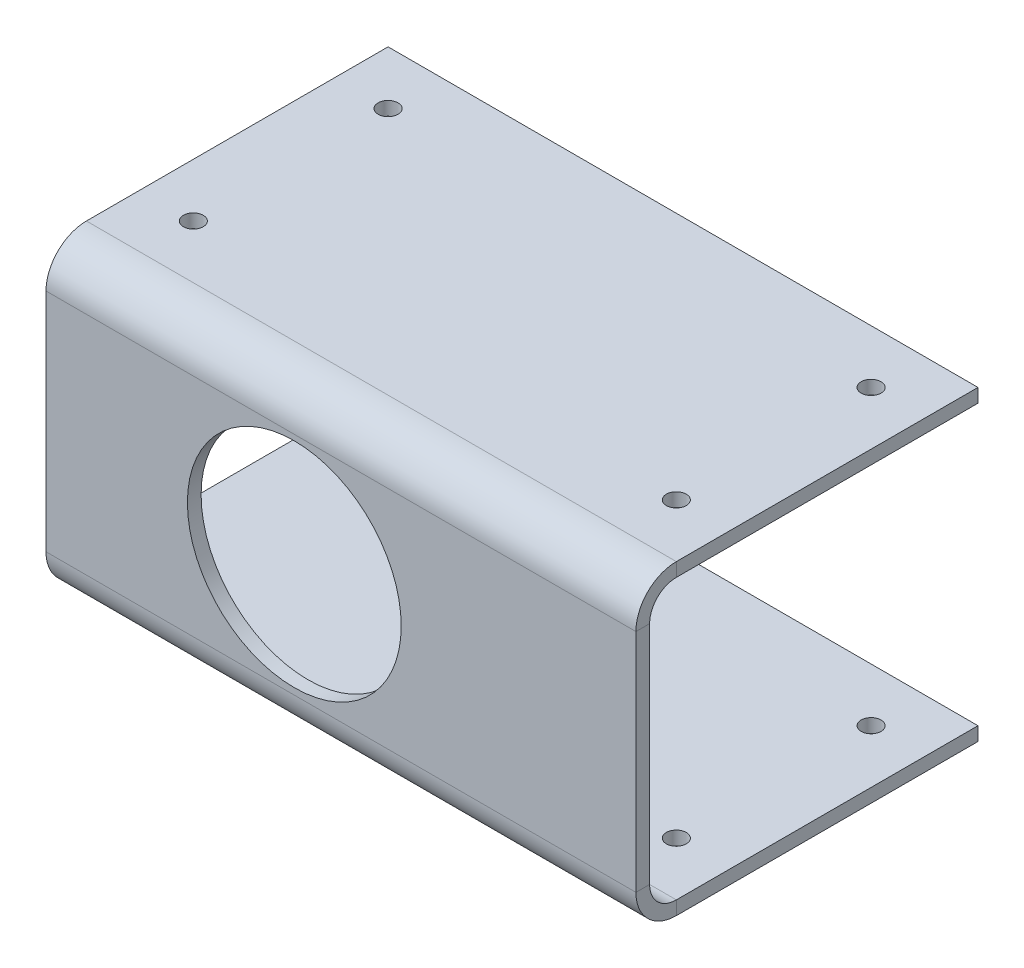
SolidWorks part; units mm, degrees
note: The reader was unsure of these and kept them because the rebuilt part matched: flange length of "Edge-Flange1".
material "6061-T6 (SS)"
ref_plane "Front Plane" through (0, 0, 0) normal (0, 0, 1) x (1, 0, 0)
ref_plane "Top Plane" through (0, 0, 0) normal (0, 1, 0) x (1, 0, 0)
ref_plane "Right Plane" through (0, 0, 0) normal (1, 0, 0) x (0, 0, -1)
sketch "Sketch1" plane through (0, 0, 0) normal (0, 0, 1) x (1, 0, 0)
  line L1 (-12.6221, 8.32) -> (16.07, 8.32)
  line L2 (-12.6221, 8.32) -> (-12.6221, -8.27)
  line L3 (-12.6221, -8.27) -> (16.07, -8.27)
  line L4 (-12.6221, -4.7) -> (-12.6221, 4.8) construction
  line L7 (16.07, -8.27) -> (22.42, -8.27)
  line L9 (16.07, 8.32) -> (22.42, 8.32)
  line L10 (22.42, -8.27) -> (22.42, 8.32)
  dimension "D1" = 6.35
base flange "Base-Flange1" sketch "Sketch1" thickness 0.8128 reverse thickness direction yes parameters "D1"=0.8128
edge flange "Edge-Flange1" sketch "Sketch10" flange profiles "Sketch10", "Sketch11" flange angle 90 flange length 20.32 flange position material outside bend radius 1.5875 thickness 0.8128 relief rectangular parameters "D6"=10, "D8"=1
sketch "Sketch10" plane through (0, -8.27, 0) normal (0, -1, 0) x (-1, 0, 0)
  line L0 (12.6221, 0) -> (-22.42, 0) construction
  line L1 (12.6221, 0) -> (-22.42, 0)
  line L2 (-22.42, 0) -> (-22.42, 19.5072)
  line L3 (-22.42, 19.5072) -> (12.6221, 19.5072)
  line L4 (12.6221, 19.5072) -> (12.6221, 0)
sketch "Sketch11" plane through (0, 8.32, 0) normal (0, 1, 0) x (1, 0, 0)
  line L0 (22.42, 0) -> (-12.6221, 0) construction
  line L1 (22.42, 0) -> (-12.6221, 0)
  line L2 (-12.6221, 0) -> (-12.6221, 19.5072)
  line L3 (-12.6221, 19.5072) -> (22.42, 19.5072)
  line L4 (22.42, 19.5072) -> (22.42, 0)
bend "EdgeBend1" bend radius 1.5875 bend angle 90 parameters "D5"=1
bend "EdgeBend2" bend radius 1.5875 bend angle 90 parameters "D5"=2
sketch "Sketch12" plane through (0, 0, 0.8128) normal (0, 0, 1) x (1, 0, 0)
  circle A0 centre (2.1279, 0.05) radius 6.35
  dimension "D1" = 12.7
extrude "Cut-Extrude1" cut sketch "Sketch12" against normal through all
hole_wizard "#56 (0.0465) Diameter Hole1" positions "Sketch14" profile "Sketch13" hole size "#56" standard "ANSI Inch" end condition through all
sketch "Sketch14" plane through (0, 9.1328, 0) normal (0, 1, 0) x (1, 0, 0)
  point P0 (19.245, 4.7625)
  point P3 (19.245, 16.3322)
  point P6 (-9.4471, 16.3322)
  point P9 (-9.4471, 4.7625)
sketch "Sketch13" plane through (19.245, 9.1328, -4.7625) normal (1, 0, 0) x (0, 0, 1)
  line L0 (0, 0) -> (0, 18.2156)
  line L1 (0, 18.2156) -> (0.5905, 18.2156)
  line L2 (0.5905, 18.2156) -> (0.5905, 0)
  line L5 (0.5905, 0) -> (0, 0)
  line L11 (0, -6.35) -> (0, 107.95) construction
  dimension "Thru Hole Dia." = 1.1811
  dimension "Thru Hole Depth" = 18.2156
sketch "Bend-Lines1" [suppressed] plane through (0, 0, 0) normal (0, 1, 0) x (1, 0, 0)
sketch "Bounding-Box1" [suppressed] plane through (0, 0, 0) normal (0, 1, 0) x (1, 0, 0)
sheet metal parameters "Sheet-Metal1" thickness 0.8128 parameters "D1"=0.8128
flat pattern "Flat-Pattern1" [suppressed]
sketch "Bend-Lines2" plane through (0, 0, 0) normal (0, 1, 0) x (1, 0, 0)
sketch3d "Bounding-Box2" [suppressed]
  line L0 (-15.97, -8.27, 0) -> (22.42, -8.27, 0) construction
  line L1 (-15.97, 8.32, 0) -> (22.42, 8.32, 0) construction
  line L2 (-15.97, -8.27, 0) -> (-15.97, 8.32, 0) construction
  line L3 (22.42, -8.27, 0) -> (22.42, 8.32, 0) construction
sheet metal parameters "Sheet-Metal2" thickness 0.8128 parameters "D1"=0.8128
flat pattern "Flat-Pattern1"
sketch "Bend-Lines2" plane through (0, 0, 0) normal (0, 0, -1) x (-1, 0, 0)
  line L0 (15.97, 7.5263) -> (-22.42, 7.5263) construction
  line L1 (-22.42, -7.4763) -> (15.97, -7.4763) construction
  line L2 (15.97, 7.5263) -> (-22.42, 7.5263) construction
  line L3 (-22.42, -7.4763) -> (15.97, -7.4763) construction
sketch3d "Bounding-Box2" [suppressed]
  line L0 (-22.42, 24.3601, 0) -> (-22.42, -24.3101, 0) construction
  line L1 (15.97, 24.3601, 0) -> (15.97, -24.3101, 0) construction
  line L2 (-22.42, 24.3601, 0) -> (15.97, 24.3601, 0) construction
  line L3 (-22.42, -24.3101, 0) -> (15.97, -24.3101, 0) construction
bend of the flat pattern "Flatten-<EdgeBend1>1"
bend of the flat pattern "Flatten-<EdgeBend2>1"
sheet metal parameters "Sheet-Metal3" thickness 0.8128 parameters "D1"=0.8128
flat pattern "Flat-Pattern1"
sketch "Bend-Lines2" plane through (0, 0, 0) normal (0, 0, -1) x (-1, 0, 0)
  line L0 (15.97, 7.5263) -> (-22.42, 7.5263) construction
  line L1 (-22.42, -7.4763) -> (15.97, -7.4763) construction
  line L2 (15.97, 7.5263) -> (-22.42, 7.5263) construction
  line L3 (-22.42, -7.4763) -> (15.97, -7.4763) construction
sketch3d "Bounding-Box2" [suppressed]
  line L0 (15.97, -18.5697, 0) -> (-22.42, -18.5697, 0) construction
  line L1 (15.97, 18.6197, 0) -> (-22.42, 18.6197, 0) construction
  line L2 (15.97, -18.5697, 0) -> (15.97, 18.6197, 0) construction
  line L3 (-22.42, -18.5697, 0) -> (-22.42, 18.6197, 0) construction
bend of the flat pattern "Flatten-<EdgeBend1>1"
bend of the flat pattern "Flatten-<EdgeBend2>1"
sheet metal parameters "Sheet-Metal4" thickness 0.8128 parameters "D1"=0.8128
flat pattern "Flat-Pattern1"
sketch "Bend-Lines2" plane through (0, 0, 0) normal (0, 0, -1) x (-1, 0, 0)
  line L0 (12.6221, 7.5263) -> (-22.42, 7.5263) construction
  line L1 (-22.42, -7.4763) -> (12.6221, -7.4763) construction
  line L2 (12.6221, 7.5263) -> (-22.42, 7.5263) construction
  line L3 (-22.42, -7.4763) -> (12.6221, -7.4763) construction
sketch3d "Bounding-Box2" [suppressed]
  line L0 (-22.42, 26.2397, 0) -> (-22.42, -26.1897, 0) construction
  line L1 (12.6221, 26.2397, 0) -> (12.6221, -26.1897, 0) construction
  line L2 (-22.42, 26.2397, 0) -> (12.6221, 26.2397, 0) construction
  line L3 (-22.42, -26.1897, 0) -> (12.6221, -26.1897, 0) construction
bend of the flat pattern "Flatten-<EdgeBend1>1"
bend of the flat pattern "Flatten-<EdgeBend2>1"
